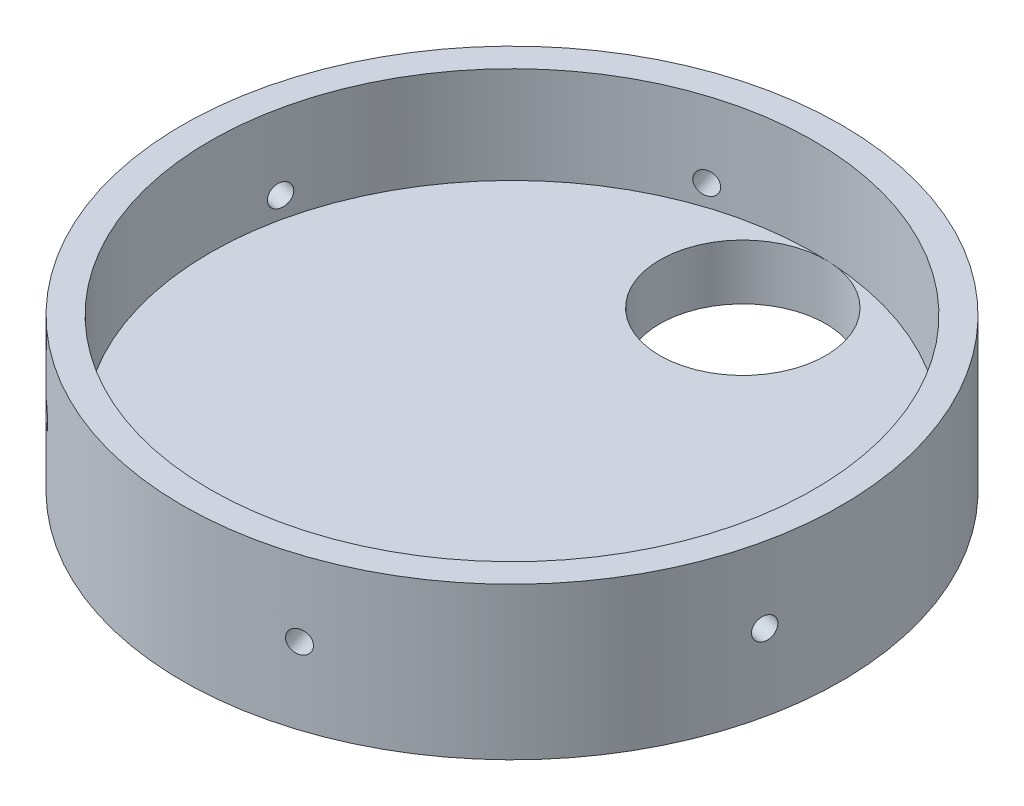
SolidWorks part; units mm, degrees
material "6061-T4 (SS)"
ref_plane "Front Plane" through (0, 0, 0) normal (0, 0, 1) x (1, 0, 0)
ref_plane "Top Plane" through (0, 0, 0) normal (0, 1, 0) x (1, 0, 0)
ref_plane "Right Plane" through (0, 0, 0) normal (1, 0, 0) x (0, 0, -1)
sketch "Sketch1" plane through (0, 0, 0) normal (0, 1, 0) x (1, 0, 0)
  circle A0 centre (0, 0) radius 75.692
  circle A1 centre (0, 0) radius 69.342
  dimension "D1" = 151.384
  dimension "D2" = 138.684
extrude "Boss-Extrude1" add sketch "Sketch1" along normal blind 22.225
sketch "Sketch2" plane through (0, 0, 0) normal (0, -1, 0) x (1, 0, 0)
  circle A0 centre (0, 0) radius 75.692
  dimension "D1" = 151.384
extrude "Boss-Extrude2" add sketch "Sketch2" along normal blind 12.7
hole_wizard "Tap Drill for 1/4-20 Tap1" positions "3DSketch2" profile "Sketch4" hole size "1/4-20" standard "ANSI Inch"
sketch3d "3DSketch2"
  line L0 (73.6526, 22.225, 17.4519) -> (73.9972, 4.8963, 15.9279)
  circle A1 centre (0, 22.225, 0) radius 75.692 construction
  point P0 (73.9972, 4.8963, 15.9279)
  point P10 (0, 97.917, 0)
  point P12 (-133.403, 50.4262, 0)
  dimension "D1" = 17.399
sketch "Sketch4" plane through (73.9972, 4.8963, 15.9279) normal (0, 1, 0) x (0.2104, 0, -0.9776)
  line L0 (0, 0) -> (0, 11.1858)
  line L1 (0, 11.1858) -> (2.5527, 9.652)
  line L2 (2.5527, 9.652) -> (2.5527, 0)
  line L5 (2.5527, 0) -> (0, 0)
  line L10 (0, 11.1858) -> (-2.5527, 9.652) construction
  line L11 (0, -6.35) -> (0, 107.95) construction
  dimension "Hole Dia." = 5.1054
  dimension "Hole Depth" = 9.652
  dimension "Drill Angle" = 118
pattern_circular "CirPattern1" count 6 over 360 about axis through (0, 22.225, 0) along (0, -1, 0) of "Tap Drill for 1/4-20 Tap1" reverse direction yes
sketch "Sketch5" plane through (0, 0, 0) normal (0, 1, 0) x (1, 0, 0)
  circle A0 centre (2.7962, 50.2142) radius 19.05
  circle A1 centre (0, 0) radius 69.342 construction
extrude "Cut-Extrude1" cut sketch "Sketch5" against normal through all
